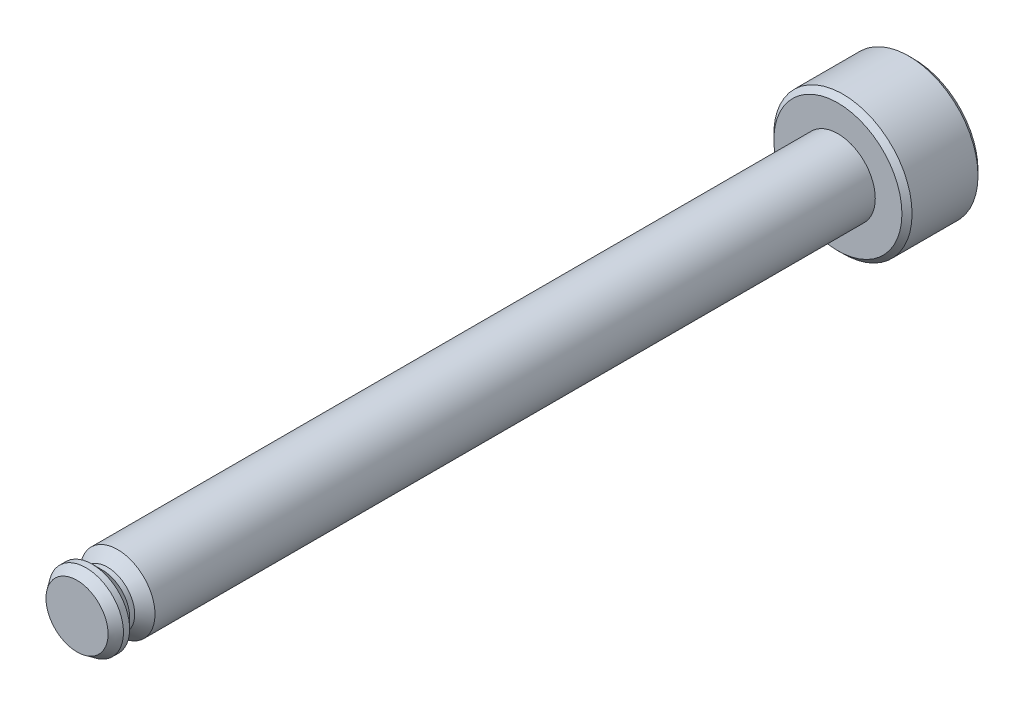
SolidWorks part; units mm, degrees
ref_plane "Front" through (0, 0, 0) normal (0, 0, 1) x (1, 0, 0)
ref_plane "Top" through (0, 0, 0) normal (0, 1, 0) x (1, 0, 0)
ref_plane "Right" through (0, 0, 0) normal (1, 0, 0) x (0, 0, -1)
sketch "Sketch2" plane through (0, 0, 0) normal (0, 0, 1) x (1, 0, 0)
  circle A0 centre (0, 0) radius 1.475
  dimension "D1" = 2.95
extrude "Shaft" add sketch "Sketch2" along normal blind 30
sketch "Sketch5" plane through (0, 0, 0) normal (0, 0, 1) x (1, 0, 0)
  circle A0 centre (0, 0) radius 2.725
  dimension "D1" = 5.45
extrude "Head" add sketch "Sketch5" against normal blind 3
sketch "Sketch4" plane through (0, 0, 0) normal (1, 0, 0) x (0, 0, -1)
  line L0 (0, 0) -> (-16.9, 0) construction
  line L1 (-16.9, 0) -> (-16.9, 4.3666) construction
  line L2 (-17.4, 1.475) -> (-16.4, 1.475)
  line L3 (0, 1.475) -> (-30, 1.475) construction
  line L6 (-16.4, 1.475) -> (-16.8, 1.075)
  line L7 (-16.8, 1.075) -> (-17, 1.075)
  line L8 (-17, 1.075) -> (-17.4, 1.475)
  line L10 (-16.9, 27.3361) -> (-16.9, -72.6639) construction
  dimension "D2" = 1
  dimension "D3" = 45
  dimension "D4" = 0.4
revolve "e-Clip Notch Short" [suppressed] cut sketch "Sketch4" angle 360 about L0
chamfer "Chamfer1" distance 0.25 angle 55 1 edges at (1.475, 0, 30) first distance on face at (1.475, 0, 30)
chamfer "Deburs" distance 0.2 angle 45 2 edges at (2.725, 0, 0) (2.725, 0, -3)
sketch "Sketch6" plane through (0, 0, 0) normal (1, 0, 0) x (0, 0, -1)
  line L0 (0, 0) -> (-28.9, 0) construction
  line L1 (-28.9, 0) -> (-28.9, 1.075) construction
  line L2 (0, 1.475) -> (-29.643, 1.475) construction
  line L3 (-29.4, 1.475) -> (-28.4, 1.475)
  line L4 (-28.4, 1.475) -> (-28.8, 1.075)
  line L5 (-28.8, 1.075) -> (-29, 1.075)
  line L6 (-29, 1.075) -> (-29.4, 1.475)
  line L7 (-28.9, 1.075) -> (-28.9, 1.475) construction
  line L8 (-17.4, 1.475) -> (-16.4, 1.475) construction
  line L9 (-17, 1.075) -> (-17.4, 1.475) construction
  line L10 (-28.9, 50) -> (-28.9, -50) construction
revolve "e-Clip Notch Long" cut sketch "Sketch6" angle 360 about L0
equation "\"D1@Sketch2\"=\"Plastic Hardware OD@Box Assy.Assembly\""
equation "\"D1@Sketch5\"=\"Hardware Head Countersink Diameter@Box Assy.Assembly\"-.3mm"
equation "\"D1@Head\"=\"Countersink Depth@Box Assy.Assembly\""
